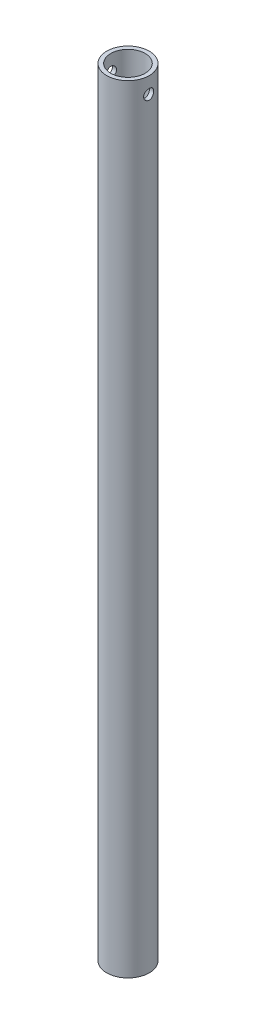
SolidWorks part; units mm, degrees
material "6061 Alloy"
ref_plane "Front Plane" through (0, 0, 0) normal (0, 0, 1) x (1, 0, 0)
ref_plane "Top Plane" through (0, 0, 0) normal (0, 1, 0) x (1, 0, 0)
ref_plane "Right Plane" through (0, 0, 0) normal (1, 0, 0) x (0, 0, -1)
sketch "Sketch1" plane through (0, 0, 0) normal (0, 1, 0) x (1, 0, 0)
  circle A0 centre (0, 0) radius 16.6687
  circle A1 centre (0, 0) radius 13.4938
  dimension "D1" = 33.3375
  dimension "D2" = 26.9875
extrude "Boss-Extrude1" add sketch "Sketch1" along normal blind 609.6
sketch "Sketch2" plane through (0, 0, 0) normal (1, 0, 0) x (0, 0, -1)
  line L0 (0, 55) -> (0, -55) construction
  line L1 (16.6687, 609.6) -> (-16.6687, 609.6) construction
  circle A0 centre (0, 596.9) radius 3.9687
  dimension "D2" = 7.9375
  dimension "D1" = 12.7
extrude "Cut-Extrude1" cut sketch "Sketch2" against normal blind 25.4 and the other way blind 25.4
